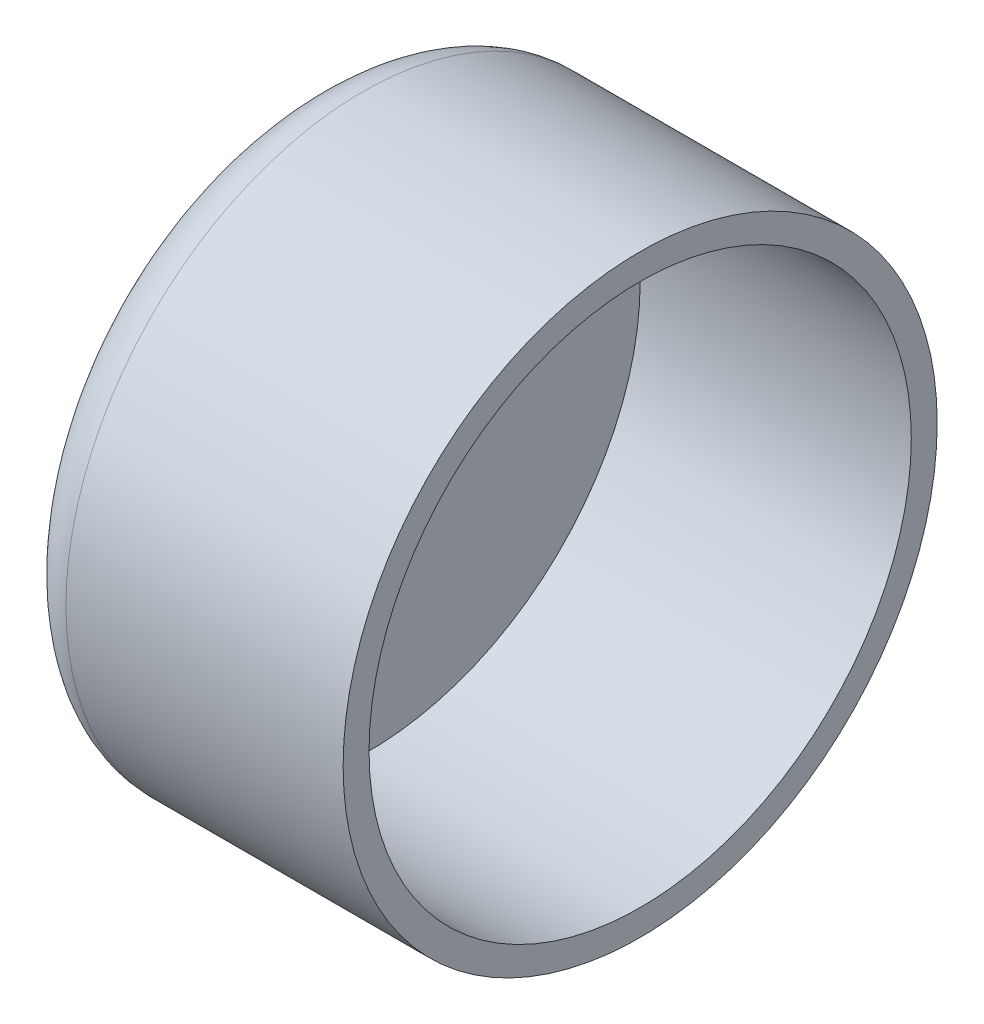
SolidWorks part; units mm, degrees
material "PE Высокой плотности"
ref_plane "Спереди" through (0, 0, 0) normal (0, 0, 1) x (1, 0, 0)
ref_plane "Сверху" through (0, 0, 0) normal (0, 1, 0) x (1, 0, 0)
ref_plane "Справа" through (0, 0, 0) normal (1, 0, 0) x (0, 0, -1)
sketch "Эскиз1" plane through (0, 0, 0) normal (1, 0, 0) x (0, 0, -1)
  circle A0 centre (0, 0) radius 45
  dimension "Dнаруж" = 90
extrude "Вытянуть-Тонкостенный1" add sketch "Эскиз1" against normal blind 45 thin contours A0 thin type one direction wall 4.3
sketch "Эскиз2" plane through (-45, 0, 0) normal (-1, 0, 0) x (0, 0, 1)
  circle A0 centre (0, 0) radius 49.3 construction
  circle A1 centre (0, 0) radius 49.3
extrude "Бобышка-Вытянуть1" add sketch "Эскиз2" along normal blind 1
dome "Купол1" faces to dome 1 distance 18 reverse direction no elliptical dome yes face at (-46, 0, 49.3) parameters "D1"=18
sketch3d "Трехмерный эскиз1"
  line L0 (-45, 0, 0) -> (0, 0, 0) construction
other "Точка соединения1" parameters "Диаметр"=90, "StubLength"=0
ref_axis "Ось2" through (-35, 0, 0) along (-1, 0, 0)
equation "\"D1@Вытянуть-Тонкостенный1\"= 1/2 * \"Dнаруж@Эскиз1\""
equation "\"D1@Купол1\"= 1/5 * \"Dнаруж@Эскиз1\""
